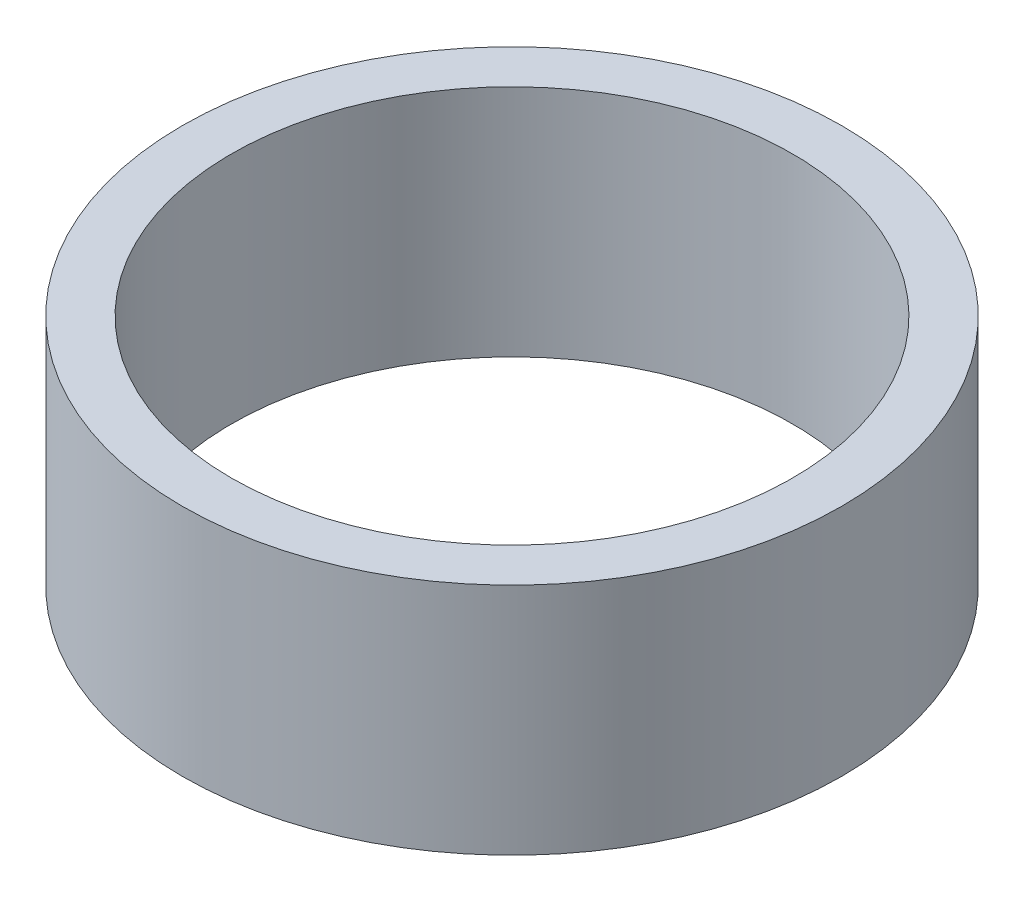
SolidWorks part; units mm, degrees
material "C (Graphite)"
ref_plane "Front Plane" through (0, 0, 0) normal (0, 0, 1) x (1, 0, 0)
ref_plane "Top Plane" through (0, 0, 0) normal (0, 1, 0) x (1, 0, 0)
ref_plane "Right Plane" through (0, 0, 0) normal (1, 0, 0) x (0, 0, -1)
sketch "Sketch1" plane through (0, 0, 0) normal (0, 1, 0) x (1, 0, 0)
  circle A0 centre (0, 0) radius 42.285
  circle A1 centre (0, 0) radius 36
  dimension "D1" = 84.57
  dimension "D2" = 72
extrude "Boss-Extrude1" add sketch "Sketch1" along normal blind 30
sketch "Sketch2" plane through (0, 0, 0) normal (0, -1, 0) x (1, 0, 0)
  circle A0 centre (0, 0) radius 37.5
  circle A1 centre (0, 0) radius 40
  dimension "D1" = 75
  dimension "D2" = 80
extrude "Cut-Extrude1" cut sketch "Sketch2" against normal blind 4.6
